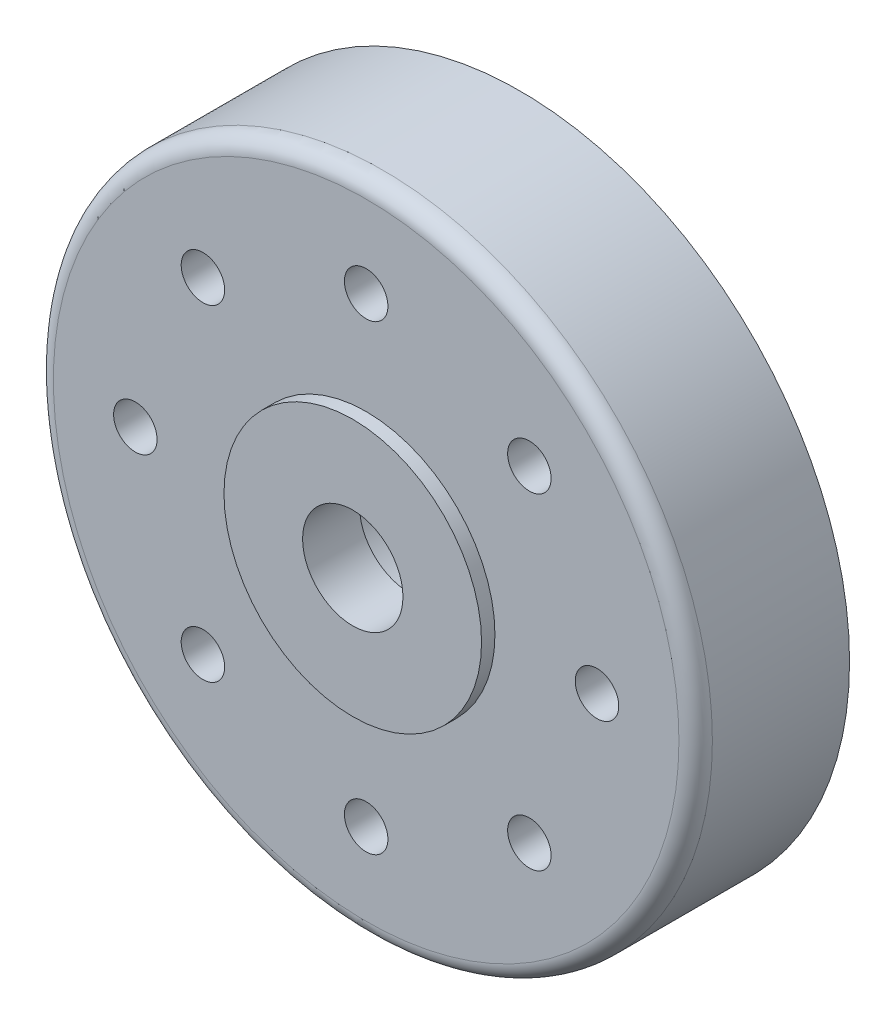
SolidWorks part; units mm, degrees
ref_plane "Front" through (0, 0, 0) normal (0, 0, 1) x (1, 0, 0)
ref_plane "Top" through (0, 0, 0) normal (0, 1, 0) x (1, 0, 0)
ref_plane "Right" through (0, 0, 0) normal (1, 0, 0) x (0, 0, -1)
sketch "Sketch1" plane through (0, 0, 0) normal (0, 0, 1) x (1, 0, 0)
  line L0 (0, 0) -> (0, 6.7) construction
  line L1 (0, 0) -> (4.879, 4.879) construction
  circle A0 centre (0, 0) radius 9.85
  circle A1 centre (0, 0) radius 1.5
  circle A2 centre (0, 6.9) radius 0.65
  circle A3 centre (4.879, 4.879) radius 0.65
  circle A4 centre (6.9, 0) radius 0.65
  circle A5 centre (4.879, -4.879) radius 0.65
  circle A6 centre (0, -6.9) radius 0.65
  circle A7 centre (-4.879, -4.879) radius 0.65
  circle A8 centre (-6.9, 0) radius 0.65
  circle A9 centre (-4.879, 4.879) radius 0.65
  dimension "D1" = 19.7
  dimension "D2" = 3
  dimension "D3" = 1.3
  dimension "D4" = 6.9
  dimension "D6" = 45
  dimension "D7" = 6.7
  dimension "D5" = 8
extrude "Boss-Extrude1" add sketch "Sketch1" along normal blind 5
sketch "Sketch4" plane through (0, 0, 0) normal (0, 0, -1) x (-1, 0, 0)
  circle A0 centre (0, 0) radius 2.5
  dimension "D1" = 5
extrude "Cut-Extrude2" cut sketch "Sketch4" against normal blind 3.3
shell "Shell1" thickness 1.4 removed face at (-2.5, 0, 0)
sketch "Sketch3" plane through (0, 0, 5) normal (0, 0, 1) x (1, 0, 0)
  circle A0 centre (0, 0) radius 9.85 construction
  circle A1 centre (0, 0) radius 9.85
  circle A3 centre (0, 0) radius 3.85
  dimension "D1" = 7.7
extrude "Cut-Extrude1" cut sketch "Sketch3" against normal blind 0.4
fillet "Fillet1" radius 0.5 1 edges at (9.85, 0, 4.6)
